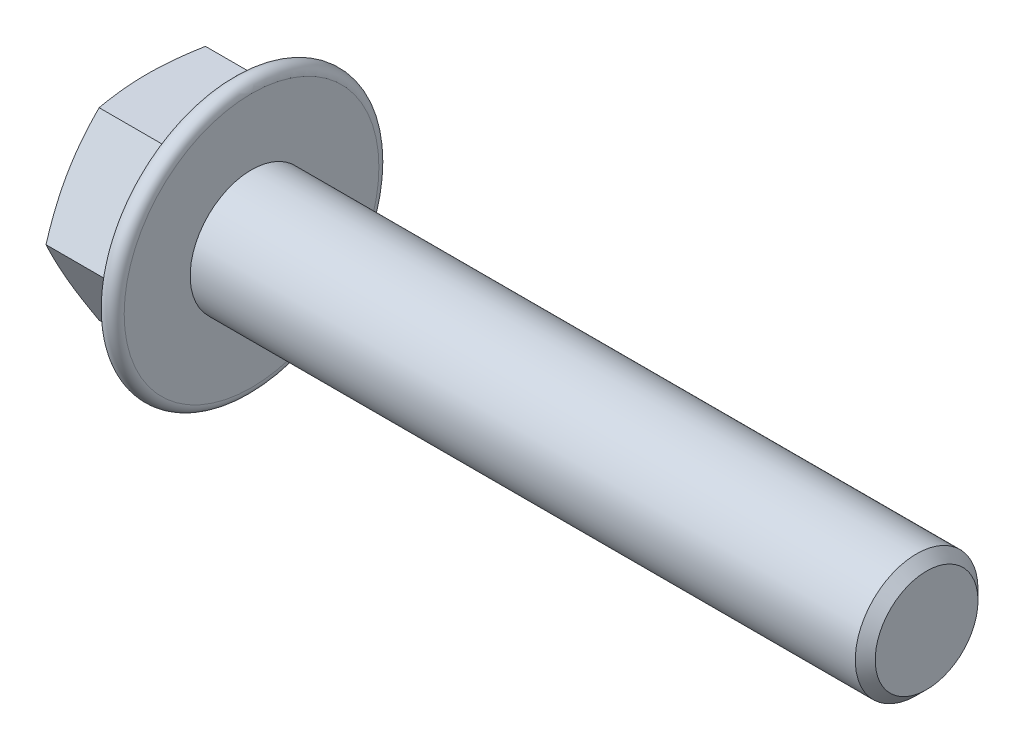
SolidWorks part; units mm, degrees
ref_plane "Front" through (0, 0, 0) normal (0, 0, 1) x (1, 0, 0)
ref_plane "Top" through (0, 0, 0) normal (0, 1, 0) x (1, 0, 0)
ref_plane "Right" through (0, 0, 0) normal (1, 0, 0) x (0, 0, -1)
sketch "Sketch1" plane through (0, 0, 0) normal (1, 0, 0) x (0, 0, -1)
  line L1 (8.6603, 0) -> (4.3301, 7.5)
  line L2 (4.3301, 7.5) -> (-4.3301, 7.5)
  line L3 (-4.3301, 7.5) -> (-8.6603, 0)
  line L4 (-8.6603, 0) -> (-4.3301, -7.5)
  line L5 (-4.3301, -7.5) -> (4.3301, -7.5)
  line L6 (4.3301, -7.5) -> (8.6603, 0)
  circle A0 centre (0, 0) radius 7.5 construction
  dimension "s" = 15
extrude "BaseHead" add sketch "Sketch1" along normal blind 9.2
ref_plane "Plane1" through (38.2, 0, 0) normal (1, 0, 0) x (0, 0, -1)
sketch "Sketch2" plane through (9.2, 0, 0) normal (1, 0, 0) x (0, 0, -1)
  circle A0 centre (0, 0) radius 5
  dimension "d" = 10
extrude "BaseBody" add sketch "Sketch2" along normal blind 55
cosmetic thread "ThreadCosmetic1" [suppressed] parameters "b"=26, "D2"=8.376
sketch "Sketch3" plane through (-0.4952, 0, 6.2687) normal (0, 1, 0) x (0, 0, -1)
  line L0 (14.929, -0.4952) -> (14.929, -1.609)
  line L2 (14.929, -1.609) -> (11.8687, -0.4952)
  line L4 (11.8687, -0.4952) -> (14.929, -0.4952)
  line L5 (6.2687, 4.1693) -> (6.2687, -11.9236) construction
  dimension "D1" = 20
  dimension "da" = 11.2
revolve "HeadChamfer" cut sketch "Sketch3" angle 360 about L5
sketch "Sketch5" plane through (-0.1752, 0, 7.2752) normal (0, 1, 0) x (0, 0, -1)
  line L0 (7.2752, -9.3752) -> (7.2752, -7.1738) construction
  line L2 (7.2752, -9.3752) -> (17.6518, -9.3752)
  line L3 (17.9163, -7.8752) -> (7.2752, -4.0021)
  line L4 (7.2752, -4.0021) -> (7.2752, -9.3752)
  line L7 (7.2752, 4.4893) -> (7.2752, -11.6035) construction
  arc A0 (17.6518, -9.3752) -> (17.9163, -7.8752) centre (17.6518, -8.6018) ccw
  dimension "D3" = 20
  dimension "c" = 1.5
  dimension "dc" = 22.3
revolve "Flange" add sketch "Sketch5" angle 360 about L0
fillet "HeadFillet" [suppressed] radius 0.4
fillet "FlangeHexFillet" radius 0.6 6 edges
chamfer "Chamfer1" distance 0.812 angle 45 1 edges at (64.2, 0, -5)
sketch "Sketch6" plane through (0, 0, 0) normal (0, 0, 1) x (1, 0, 0)
  line L0 (62.576, 5.812) -> (63.388, 5.812)
  line L1 (63.388, 5.812) -> (63.388, 5)
  line L2 (63.388, 5) -> (62.982, 4.2968)
  line L3 (62.982, 4.2968) -> (62.576, 5)
  line L4 (62.576, 5) -> (62.576, 5.812)
  line L5 (63.388, 5) -> (9.2, 5) construction
  dimension "D1" = 0.812
revolve "Cut-Revolve10" [suppressed] cut sketch "Sketch6" angle 360
pattern_linear "LPattern10" [suppressed] count 27 of bodies 106
equation "\"D1@Chamfer1\" = (  \"d@Sketch2\" - \"D2@ThreadCosmetic1\" )  / 2"
equation "\"b@ThreadCosmetic1\" = \"l@BaseBody\" - \"lg@Plane1\""
equation "\"da@Sketch3\" = \"s@Sketch1\""
equation "\"D1@Sketch6\" =  ( \"d@Sketch2\" - \"D2@ThreadCosmetic1\" )  / 2"
equation "\"pitch@LPattern10\" = 1.2 * \"D1@Sketch6\""
equation "\"D1@LPattern10\" = \"b@ThreadCosmetic1\" / \"pitch@LPattern10\""
